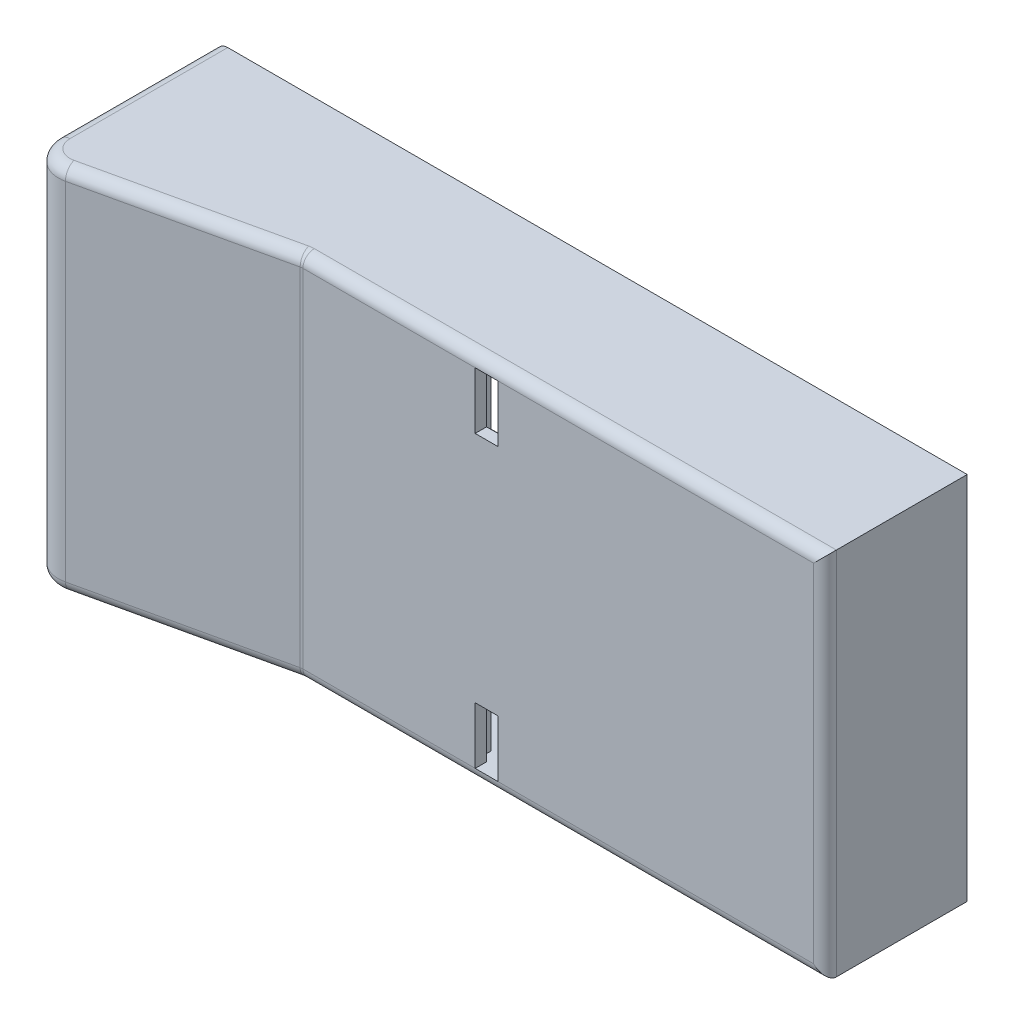
SolidWorks part; units mm, degrees
other "Markup1"
sketch "Sketch6" plane through (-132, 65, -25) normal (-0.6968, 0.4309, -0.5733) x (0.6979, 0.5918, -0.4034)
ref_plane "Front Plane" through (0, 0, 0) normal (0, 0, 1) x (1, 0, 0)
ref_plane "Top Plane" through (0, 0, 0) normal (0, 1, 0) x (1, 0, 0)
ref_plane "Right Plane" through (0, 0, 0) normal (1, 0, 0) x (0, 0, -1)
sketch "Sketch3" plane through (0, 0, 0) normal (0, 1, 0) x (1, 0, 0)
  line L0 (0, 0) -> (0, 25)
  line L1 (0, 25) -> (-2, 25)
  line L2 (-2, 25) -> (-2, 2)
  line L3 (-2, 2) -> (-92, 2)
  line L5 (-92, 0) -> (0, 0)
  line L6 (-130, -6.55) -> (-92, 2)
  line L7 (-132, -9) -> (-132, 25)
  line L8 (-132, -9) -> (-92, 0)
  line L9 (-132, 25) -> (-130, 25)
  line L10 (-130, 25) -> (-130, -6.55)
extrude "Boss-Extrude3" add sketch "Sketch3" along normal blind 65
sketch "Sketch4" plane through (0, 0, -25) normal (0, 0, -1) x (-1, 0, 0)
  line L0 (2, 65) -> (2, 0) construction
  line L1 (130, 65) -> (2, 65)
  line L2 (130, 65) -> (130, 63)
  line L3 (130, 63) -> (2, 63)
  line L4 (2, 65) -> (2, 63)
  line L5 (2, 2) -> (2, 0)
  line L6 (130, 0) -> (2, 0)
  line L7 (130, 2) -> (130, 0)
  line L8 (130, 2) -> (2, 2)
extrude "Boss-Extrude4" add sketch "Sketch4" against normal up to body separate body
sketch "Sketch5" plane through (-132, 0, 0) normal (-1, 0, 0) x (0, 0, 1)
  line L4 (-8, 5.7203) -> (-20, 5.7203)
  line L5 (-8, 5.7203) -> (-8, 59.2797)
  line L6 (-8, 59.2797) -> (-20, 59.2797)
  line L7 (-20, 5.7203) -> (-20, 59.2797)
  line L8 (-8, 5.7203) -> (-20, 59.2797) construction
  line L9 (-8, 59.2797) -> (-20, 5.7203) construction
  point P6 (-14, 32.5)
extrude "Cut-Extrude2" cut sketch "Sketch5" against normal blind 11
fillet "Fillet1" radius 5 1 edges at (-132, 32.5, 9)
fillet "Fillet2" radius 2 10 edges at (-132, 65, -11.125) (-132, 0, -11.125) (-130.1235, 65, 6.6543) (-130.1235, 0, 6.6543) (-108.9512, 65, 3.814) (-108.9512, 0, 3.814) (-92, 32.5, 0) (-46, 65, 0) (-46, 0, 0) (0, 32.5, 0)
sketch "Sketch7" plane through (0, 0, -2) normal (0, 0, -1) x (-1, 0, 0)
  line L2 (92, 63) -> (2, 63)
  line L3 (92, 63) -> (92, 2)
  line L4 (92, 2) -> (2, 2)
  line L5 (2, 63) -> (2, 2)
  point P7 (79.5, 32.5)
extrude "Boss-Extrude5" add sketch "Sketch7" along normal blind 2
sketch "Sketch11" plane through (0, 0, -25) normal (0, 0, -1) x (-1, 0, 0)
  line L0 (2, 63) -> (130, 63) construction
  line L1 (130, 63) -> (130, 2) construction
  line L2 (7, 63) -> (2, 63)
  line L3 (2, 63) -> (2, 58)
  line L4 (2, 7) -> (2, 2)
  line L5 (2, 2) -> (7, 2)
  line L6 (125, 2) -> (130, 2)
  line L7 (130, 2) -> (130, 7)
  line L8 (125, 63) -> (130, 63)
  line L9 (130, 63) -> (130, 58)
  arc A0 (125, 63) -> (130, 58) centre (130, 63) ccw
  arc A1 (7, 63) -> (2, 58) centre (2, 63) cw
  arc A2 (7, 2) -> (2, 7) centre (2, 2) ccw
  arc A3 (125, 2) -> (130, 7) centre (130, 2) cw
extrude "Boss-Extrude6" add sketch "Sketch11" against normal blind 5
sketch "Sketch12" plane through (0, 0, -25) normal (0, 0, -1) x (-1, 0, 0)
  circle A1 centre (3.7678, 61.2322) radius 1.5
  circle A2 centre (128.2322, 61.2322) radius 1.5
  circle A3 centre (128.2322, 3.7678) radius 1.5
  circle A4 centre (3.7678, 3.7678) radius 1.5
extrude "Cut-Extrude5" cut sketch "Sketch12" against normal blind 20
sketch "Sketch14" plane through (0, 0, -4) normal (0, 0, -1) x (-1, 0, 0)
  line L0 (2, 58) -> (2, 63)
  line L1 (92, 63) -> (2, 63) construction
  line L2 (2, 63) -> (2, 2) construction
  line L3 (2, 63) -> (7, 63)
  line L5 (2, 2) -> (7, 2)
  line L6 (2, 7) -> (2, 2)
  arc A0 (7, 63) -> (2, 58) centre (2, 63) cw
  arc A1 (7, 2) -> (2, 7) centre (2, 2) ccw
extrude "Boss-Extrude7" add sketch "Sketch14" along normal blind 13
sketch "Sketch15" plane through (0, 0, -25) normal (0, 0, -1) x (-1, 0, 0)
  circle A0 centre (3.7678, 3.7678) radius 1.5
  circle A1 centre (3.7678, 61.2322) radius 1.5
extrude "Cut-Extrude6" cut sketch "Sketch15" against normal blind 21
sketch "Sketch16" plane through (0, 0, -4) normal (0, 0, -1) x (-1, 0, 0)
  line L0 (62.75, 2) -> (56.25, 2)
  line L2 (62.75, 63) -> (56.25, 63)
  line L3 (59.5, 59.75) -> (59.5, 5.25)
  line L4 (62.75, 2) -> (62.75, 63)
  line L5 (7, 2) -> (92, 2) construction
  line L6 (92, 63) -> (7, 63) construction
  line L7 (56.25, 2) -> (56.25, 63)
  point P9 (59.5, 32.5)
extrude "Cut-Extrude7" cut sketch "Sketch16" against normal blind 2 contours L7 L4 region at (-59.5, 2.6135, -4)
sketch "Sketch17" plane through (0, 0, -2) normal (0, 0, -1) x (-1, 0, 0)
  line L11 (62.75, 63) -> (56.25, 63) construction
  line L12 (59.5, 53) -> (61.5, 53)
  line L13 (61.5, 53) -> (61.5, 63)
  line L14 (59.5, 53) -> (57.5, 53)
  line L15 (57.5, 53) -> (57.5, 63)
  line L16 (57.5, 63) -> (61.5, 63)
  line L18 (57.5, 2) -> (61.5, 2)
  line L19 (57.5, 12) -> (57.5, 2)
  line L20 (59.5, 12) -> (57.5, 12)
  line L21 (61.5, 12) -> (61.5, 2)
  line L22 (59.5, 12) -> (61.5, 12)
fillet "Fillet3" radius 3 1 edges at (-92, 32.5, -2)
fillet "Fillet4" radius 3 1 edges at (-92, 32.5, -4)
extrude "Cut-Extrude9" cut sketch "Sketch17" against normal blind 2
sketch "Sketch18" plane through (0, 0, -2) normal (0, 0, -1) x (-1, 0, 0)
  line L1 (56.25, 2) -> (56.25, 63) construction
  line L4 (62.75, 13.9481) -> (56.25, 13.9481)
  line L5 (62.75, 13.9481) -> (62.75, 51.0519)
  line L6 (62.75, 51.0519) -> (56.25, 51.0519)
  line L7 (56.25, 13.9481) -> (56.25, 51.0519)
  line L8 (62.75, 13.9481) -> (56.25, 51.0519) construction
  line L9 (62.75, 51.0519) -> (56.25, 13.9481) construction
  point P6 (59.5, 32.5)
extrude "Boss-Extrude8" add sketch "Sketch18" along normal blind 2
